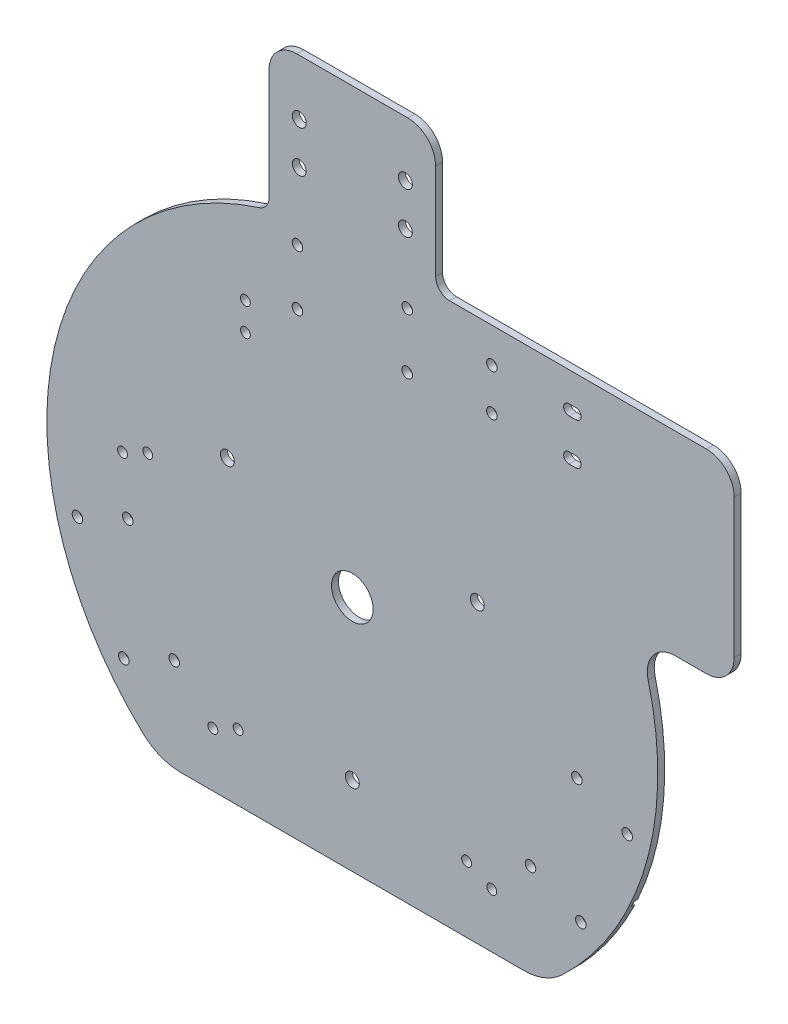
SolidWorks part; units mm, degrees
ref_plane "Front Plane" through (0, 0, 0) normal (0, 0, 1) x (1, 0, 0)
ref_plane "Top Plane" through (0, 0, 0) normal (0, 1, 0) x (1, 0, 0)
ref_plane "Right Plane" through (0, 0, 0) normal (1, 0, 0) x (0, 0, -1)
sketch "Sketch1" plane through (0, 0, 0) normal (0, 0, 1) x (1, 0, 0)
  line L0 (0, 139.7) -> (139.7, 139.7)
  line L2 (139.7, 139.7) -> (174.625, 139.7)
  line L3 (174.625, 139.7) -> (174.625, 50.7007)
  line L4 (174.625, 50.7007) -> (130.175, 50.7007)
  arc A0 (0, 139.7) -> (130.175, 50.7007) centre (0, 0) ccw
  dimension "D1" = 279.4
  dimension "D2" = 139.7
  dimension "D3" = 34.925
  dimension "D4" = 44.45
extrude "Boss-Extrude1" add sketch "Sketch1" along normal blind 3.175
sketch "Sketch2" plane through (0, 0, 0) normal (0, 0, -1) x (-1, 0, 0)
  line L0 (0, -139.7) -> (0, 139.7) construction
  line L1 (-139.7, 0) -> (139.7, 0) construction
  line L2 (-126.6112, -59.0398) -> (-126.6112, 0) construction
  line L3 (126.6112, -59.0398) -> (126.6112, 0) construction
  line L4 (-57.15, 26.6495) -> (0, -72.3372) construction
  line L5 (-126.6112, -59.0398) -> (126.6112, 59.0398) construction
  line L6 (126.6112, -59.0398) -> (-126.6112, 59.0398) construction
  line L7 (-125.9403, -60.4785) -> (127.2821, 57.601)
  line L8 (127.2821, -57.601) -> (-125.9403, 60.4785)
  line L9 (1.5875, -139.7) -> (1.5875, 139.7)
  line L10 (-127.2821, -57.601) -> (125.9403, 60.4785)
  line L11 (125.9403, -60.4785) -> (-127.2821, 57.601)
  line L12 (-1.5875, -139.7) -> (-1.5875, 139.7)
  line L13 (0, -72.3372) -> (57.15, 26.6495) construction
  line L14 (57.15, 26.6495) -> (-57.15, 26.6495) construction
  line L15 (0, 139.7) -> (-174.625, 139.7)
  line L16 (0, 139.7) -> (-174.625, 139.7)
  line L17 (-174.625, 139.7) -> (-174.625, 50.7007)
  line L19 (-121.527, -54.9174) -> (-120.1852, -57.7949)
  line L20 (-120.1852, 57.7949) -> (-121.527, 54.9174)
  line L21 (120.1852, 57.7949) -> (121.527, 54.9174)
  line L22 (-174.625, 139.7) -> (-174.625, 50.7007)
  line L23 (-174.625, 50.7007) -> (-130.175, 50.7007)
  line L24 (-174.625, 50.7007) -> (-130.175, 50.7007)
  line L25 (121.527, -54.9174) -> (120.1852, -57.7949)
  line L26 (-1.5875, 133.35) -> (1.5875, 133.35)
  circle A0 centre (0, 0) radius 139.7 construction
  arc A2 (-130.175, 50.7007) -> (0, 139.7) centre (0, 0) ccw
  arc A3 (-130.175, 50.7007) -> (0, 139.7) centre (0, 0) ccw
  circle A4 centre (-57.15, 26.6495) radius 3.175
  circle A5 centre (57.15, 26.6495) radius 3.175
  circle A6 centre (0, -72.3372) radius 3.175
  point P6 (0, 0)
  point P11 (0, 0)
  arc M9 (-130.175, 50.7007) -> (0, 139.7) centre (0, 0) ccw
  line M24 (0, 139.7) -> (-174.625, 139.7)
  dimension "D5" = 6.35
  dimension "D1" = 25
  dimension "D6" = 114.3
  dimension "D7" = 6.35
  dimension "D8" = 6.35
  dimension "D9" = 6.35
  dimension "D10" = 6.35
  dimension "D11" = 6.35
  dimension "D2" = 1.5875
  dimension "D3" = 1.5875
  dimension "D4" = 0
extrude "Cut-Extrude3" cut sketch "Sketch2" against normal blind 1.5875 contours L12 L7 L11 | L12 L11 L7 L9 L8 L10 | L11 L9 L7 | L11 L12 L10 | L12 L10 L8 | L10 L8 L9 | L9 L7 L8 | L19 L10 L7 M9 | L10 L21 L7 M9 | L8 L25 L11 M9 | L12 L26 L9 M9 M24 region at (123.7323, -57.6973, 0) region at (1.0583, -1.7516, 0) region at (0, 0, 0) region at (-1.0583, -1.7516, 0) region at (2.3104, 0, 0) region at (-123.7323, -57.6973, 0) region at (-2.3104, 0, 0) region at (1.0583, 1.7516, 0) region at (-1.0583, 1.7516, 0) region at (0.0003, 136.5242, 0) region at (-123.7323, 57.6973, 0)
sketch "Sketch3" plane through (0, 0, 3.175) normal (0, 0, 1) x (1, 0, 0)
  circle A0 centre (0, 0) radius 9.525
  dimension "D1" = 19.05
extrude "Cut-Extrude4" cut sketch "Sketch3" against normal through all
extrude "Cut-Extrude5" cut sketch "Sketch2<4>" against normal through all contours L8 A4 L11 | L11 A4 | L8 A4 | L7 A5 L10 | L10 A5 | L7 A5 | L12 A6 | L9 A6 L12 | L9 A6 region at (2.2384, -72.3372, 0) region at (0, -72.3372, 0) region at (-2.2384, -72.3372, 0) region at (58.096, 24.6208, 0) region at (57.15, 26.6495, 0) region at (-57.15, 26.6495, 0) region at (-58.096, 24.6208, 0) region at (56.204, 28.6782, 0) region at (-56.204, 28.6782, 0)
sketch "Sketch2<4>" plane through (0, 0, 0) normal (0, 0, -1) x (-1, 0, 0) same geometry as "Sketch2"
sketch "Sketch4" plane through (0, 0, 3.175) normal (0, 0, 1) x (1, 0, 0)
  line L0 (86.721, 139.7) -> (86.721, 88.9)
  line L1 (86.721, 88.9) -> (139.7, 88.9)
  line L2 (130.175, 50.7007) -> (174.625, 50.7007)
  line L3 (174.625, 139.7) -> (0, 139.7)
  line L5 (174.625, 139.7) -> (0, 139.7)
  line L9 (130.175, 50.7007) -> (174.625, 50.7007)
  line L10 (174.625, 50.7007) -> (174.625, 139.7)
  line L11 (174.625, 50.7007) -> (174.625, 139.7)
  arc A3 (0, 139.7) -> (130.175, 50.7007) centre (0, 0) ccw
  arc A5 (0, 139.7) -> (130.175, 50.7007) centre (0, 0) ccw
  dimension "D3" = 50.8
  dimension "D1" = 0
sketch "Sketch8" plane through (0, 0, 3.175) normal (0, 0, 1) x (1, 0, 0)
  circle A0 centre (25.0825, 101.6) radius 2.413 construction
  circle A1 centre (-25.0825, 101.6) radius 2.413 construction
  circle A2 centre (-25.0825, 127) radius 2.413 construction
  circle A3 centre (25.0825, 127) radius 2.413 construction
  circle A4 centre (102.6812, -20.2056) radius 2.413 construction
  circle A5 centre (125.7014, -30.9401) radius 2.413 construction
  circle A6 centre (81.4805, -65.6705) radius 2.413 construction
  circle A7 centre (104.5008, -76.405) radius 2.413 construction
  circle A8 centre (-81.4805, -65.6705) radius 2.413 construction
  circle A9 centre (-104.5008, -76.405) radius 2.413 construction
  circle A10 centre (-102.6812, -20.2056) radius 2.413 construction
  circle A11 centre (-125.7014, -30.9401) radius 2.413 construction
  circle A12 centre (25.0825, 101.6) radius 2.413
  circle A13 centre (-25.0825, 101.6) radius 2.413
  circle A14 centre (-25.0825, 127) radius 2.413
  circle A15 centre (25.0825, 127) radius 2.413
  circle A16 centre (102.6812, -20.2056) radius 2.413
  circle A17 centre (125.7014, -30.9401) radius 2.413
  circle A18 centre (81.4805, -65.6705) radius 2.413
  circle A19 centre (104.5008, -76.405) radius 2.413
  circle A20 centre (-81.4805, -65.6705) radius 2.413
  circle A21 centre (-104.5008, -76.405) radius 2.413
  circle A22 centre (-102.6812, -20.2056) radius 2.413
  circle A23 centre (-125.7014, -30.9401) radius 2.413
extrude "Cut-Extrude7" cut sketch "Sketch8" against normal through all
sketch "Sketch9" plane through (0, 0, 3.175) normal (0, 0, 1) x (1, 0, 0)
  line L0 (102.235, 123.825) -> (99.06, 123.825) construction
  line L1 (102.235, 121.412) -> (99.06, 121.412)
  line L2 (102.235, 126.238) -> (99.06, 126.238)
  line L3 (100.6475, 123.825) -> (100.6475, 104.775) construction
  line L4 (100.6475, 114.3) -> (63.8175, 114.3) construction
  line L6 (102.235, 104.775) -> (99.06, 104.775) construction
  line L7 (102.235, 107.188) -> (99.06, 107.188)
  line L8 (102.235, 102.362) -> (99.06, 102.362)
  circle A2 centre (100.6475, 104.775) radius 2.413 construction
  circle A3 centre (100.6475, 123.825) radius 2.413 construction
  circle A4 centre (63.8175, 104.775) radius 2.413 construction
  circle A5 centre (63.8175, 123.825) radius 2.413 construction
  circle A8 centre (100.6475, 104.775) radius 2.413
  circle A9 centre (100.6475, 123.825) radius 2.413
  circle A10 centre (63.8175, 104.775) radius 2.413
  circle A11 centre (63.8175, 123.825) radius 2.413
  arc A12 (102.235, 121.412) -> (102.235, 126.238) centre (102.235, 123.825) ccw
  arc A13 (99.06, 126.238) -> (99.06, 121.412) centre (99.06, 123.825) ccw
  arc A14 (102.235, 107.188) -> (102.235, 102.362) centre (102.235, 104.775) cw
  arc A15 (99.06, 102.362) -> (99.06, 107.188) centre (99.06, 104.775) cw
  point P20 (100.6475, 123.825)
  point P29 (100.6475, 104.775)
  dimension "D1" = 4.826
  dimension "D2" = 3.175
extrude "Cut-Extrude8" cut sketch "Sketch9" against normal through all contours A9 | A11 | A10 | A8 | L2 A13 L1 A9 | L1 A12 L2 A9 | A15 L8 A8 L7 | A14 L7 A8 L8 region at (103.3364, 123.825, 3.175) region at (97.9586, 123.825, 3.175) region at (100.6475, 123.825, 3.175) region at (103.3364, 104.775, 3.175) region at (97.9586, 104.775, 3.175) region at (100.6475, 104.775, 3.175) region at (63.8175, 104.775, 3.175) region at (63.8175, 123.825, 3.175)
fillet "Fillet1" radius 12.7 3 edges at (174.625, 50.7007, 1.5875) (174.625, 139.7, 1.5875) (130.175, 50.7007, 1.5875)
sketch "Sketch10" plane through (0, 0, 3.175) normal (0, 0, 1) x (1, 0, 0)
  line L0 (-87.8942, -108.585) -> (87.8942, -108.585)
  line L3 (147.5863, 50.7007) -> (161.925, 50.7007)
  line L4 (174.625, 63.4007) -> (174.625, 127)
  line L5 (161.925, 139.7) -> (0, 139.7)
  line L6 (147.5863, 50.7007) -> (161.925, 50.7007)
  line L7 (174.625, 63.4007) -> (174.625, 127)
  line L8 (161.925, 139.7) -> (0, 139.7)
  arc A4 (161.925, 50.7007) -> (174.625, 63.4007) centre (161.925, 63.4007) ccw
  arc A5 (174.625, 127) -> (161.925, 139.7) centre (161.925, 127) ccw
  arc A6 (0, 139.7) -> (135.2874, 34.834) centre (0, 0) ccw
  arc A7 (147.5863, 50.7007) -> (135.2874, 34.834) centre (147.5863, 38.0007) ccw
  arc A8 (161.925, 50.7007) -> (174.625, 63.4007) centre (161.925, 63.4007) ccw
  arc A9 (174.625, 127) -> (161.925, 139.7) centre (161.925, 127) ccw
  arc A10 (0, 139.7) -> (135.2874, 34.834) centre (0, 0) ccw
  arc A11 (147.5863, 50.7007) -> (135.2874, 34.834) centre (147.5863, 38.0007) ccw
  arc M36 (0, 139.7) -> (135.2874, 34.834) centre (0, 0) ccw
  dimension "D2" = 108.585
  dimension "D1" = 0
extrude "Cut-Extrude9" cut sketch "Sketch10" against normal through all contours L0 M36 region at (0, -121.158, 3.175)
fillet "Fillet2" radius 25.4 2 edges at (87.8942, -108.585, 1.5875) (-87.8942, -108.585, 1.5875)
sketch "Sketch11" plane through (0, 0, 3.175) normal (0, 0, 1) x (1, 0, 0)
  circle A0 centre (52.2526, -78.3155) radius 2.032 construction
  circle A1 centre (63.7627, -83.6827) radius 2.032 construction
  circle A2 centre (-48.895, 80.4545) radius 2.032 construction
  circle A3 centre (-48.895, 93.1545) radius 2.032 construction
  circle A4 centre (-63.7627, -83.6827) radius 2.032 construction
  circle A5 centre (-52.2526, -78.3155) radius 2.032 construction
  circle A6 centre (-105.0906, 4.9451) radius 2.032 construction
  circle A7 centre (-93.5805, 10.3124) radius 2.032 construction
  circle A8 centre (52.2526, -78.3155) radius 2.032 construction
  circle A9 centre (63.7627, -83.6827) radius 2.032 construction
  circle A10 centre (-48.895, 80.4545) radius 2.032 construction
  circle A11 centre (-48.895, 93.1545) radius 2.032 construction
  circle A12 centre (-63.7627, -83.6827) radius 2.032 construction
  circle A13 centre (-52.2526, -78.3155) radius 2.032 construction
  circle A14 centre (-105.0906, 4.9451) radius 2.032 construction
  circle A15 centre (-93.5805, 10.3124) radius 2.032 construction
  circle A16 centre (-93.5805, 10.3124) radius 2.2479
  circle A17 centre (-105.0906, 4.9451) radius 2.2479
  circle A18 centre (-52.2526, -78.3155) radius 2.2479
  circle A19 centre (-63.7627, -83.6827) radius 2.2479
  circle A20 centre (52.2526, -78.3155) radius 2.2479
  circle A21 centre (63.7627, -83.6827) radius 2.2479
  circle A22 centre (-48.895, 93.1545) radius 2.2479
  circle A23 centre (-48.895, 80.4545) radius 2.2479
  dimension "D1" = 4.4958
extrude "Cut-Extrude10" cut sketch "Sketch11" against normal through all
sketch "Sketch12" plane through (0, 0, 0) normal (0, 0, -1) x (-1, 0, 0)
  line L0 (0, 0) -> (0, 50000) construction
  line L1 (-24.257, 9.525) -> (24.257, 9.525) construction
  line L2 (-24.257, 9.525) -> (-24.257, -9.525) construction
  line L3 (-24.257, -9.525) -> (24.257, -9.525) construction
  line L4 (24.257, 9.525) -> (24.257, -9.525) construction
  line L5 (-24.257, 9.525) -> (24.257, -9.525) construction
  line L6 (-24.257, -9.525) -> (24.257, 9.525) construction
  line L22 (-78.3884, -108.585) -> (78.3884, -108.585)
  line L23 (125.9321, -60.4747) -> (120.1852, -57.7949)
  line L24 (120.1852, -57.7949) -> (121.527, -54.9174)
  line L25 (121.527, -54.9174) -> (127.2739, -57.5972)
  line L26 (127.2739, 57.5972) -> (121.527, 54.9174)
  line L27 (121.527, 54.9174) -> (120.1852, 57.7949)
  line L28 (120.1852, 57.7949) -> (125.9321, 60.4747)
  line L29 (1.5875, 139.691) -> (1.5875, 133.35)
  line L30 (1.5875, 133.35) -> (-1.5875, 133.35)
  line L31 (-1.5875, 133.35) -> (-1.5875, 139.7)
  line L32 (-1.5875, 139.7) -> (-161.925, 139.7)
  line L33 (-174.625, 127) -> (-174.625, 63.4007)
  line L34 (-161.925, 50.7007) -> (-147.5863, 50.7007)
  line L35 (-127.2739, -57.5972) -> (-121.527, -54.9174)
  line L36 (-121.527, -54.9174) -> (-120.1852, -57.7949)
  line L37 (-120.1852, -57.7949) -> (-125.9321, -60.4747)
  line L38 (-78.3884, -108.585) -> (78.3884, -108.585)
  line L39 (125.9321, -60.4747) -> (120.1852, -57.7949)
  line L40 (120.1852, -57.7949) -> (121.527, -54.9174)
  line L41 (121.527, -54.9174) -> (127.2739, -57.5972)
  line L42 (127.2739, 57.5972) -> (121.527, 54.9174)
  line L43 (121.527, 54.9174) -> (120.1852, 57.7949)
  line L44 (120.1852, 57.7949) -> (125.9321, 60.4747)
  line L45 (1.5875, 139.691) -> (1.5875, 133.35)
  line L46 (1.5875, 133.35) -> (-1.5875, 133.35)
  line L47 (-1.5875, 133.35) -> (-1.5875, 139.7)
  line L48 (-1.5875, 139.7) -> (-161.925, 139.7)
  line L49 (-174.625, 127) -> (-174.625, 63.4007)
  line L50 (-161.925, 50.7007) -> (-147.5863, 50.7007)
  line L51 (-127.2739, -57.5972) -> (-121.527, -54.9174)
  line L52 (-121.527, -54.9174) -> (-120.1852, -57.7949)
  line L53 (-120.1852, -57.7949) -> (-125.9321, -60.4747)
  circle A0 centre (-24.257, 9.525) radius 3.175
  circle A1 centre (24.257, 9.525) radius 3.175
  circle A2 centre (24.257, -9.525) radius 3.175
  circle A3 centre (-24.257, -9.525) radius 3.175
  arc A14 (-125.9321, -60.4747) -> (-95.8081, -101.6706) centre (0, 0) ccw
  arc A15 (-95.8081, -101.6706) -> (-78.3884, -108.585) centre (-78.3884, -83.185) ccw
  arc A16 (78.3884, -108.585) -> (95.8081, -101.6706) centre (78.3884, -83.185) ccw
  arc A17 (95.8081, -101.6706) -> (125.9321, -60.4747) centre (0, 0) ccw
  arc A18 (127.2739, -57.5972) -> (127.2739, 57.5972) centre (0, 0) ccw
  arc A19 (125.9321, 60.4747) -> (1.5875, 139.691) centre (0, 0) ccw
  arc A20 (-161.925, 139.7) -> (-174.625, 127) centre (-161.925, 127) ccw
  arc A21 (-174.625, 63.4007) -> (-161.925, 50.7007) centre (-161.925, 63.4007) ccw
  arc A22 (-135.2874, 34.834) -> (-147.5863, 50.7007) centre (-147.5863, 38.0007) ccw
  arc A23 (-135.2874, 34.834) -> (-127.2739, -57.5972) centre (0, 0) ccw
  arc A24 (-125.9321, -60.4747) -> (-95.8081, -101.6706) centre (0, 0) ccw
  arc A25 (-95.8081, -101.6706) -> (-78.3884, -108.585) centre (-78.3884, -83.185) ccw
  arc A26 (78.3884, -108.585) -> (95.8081, -101.6706) centre (78.3884, -83.185) ccw
  arc A27 (95.8081, -101.6706) -> (125.9321, -60.4747) centre (0, 0) ccw
  arc A28 (127.2739, -57.5972) -> (127.2739, 57.5972) centre (0, 0) ccw
  arc A29 (125.9321, 60.4747) -> (1.5875, 139.691) centre (0, 0) ccw
  arc A30 (-161.925, 139.7) -> (-174.625, 127) centre (-161.925, 127) ccw
  arc A31 (-174.625, 63.4007) -> (-161.925, 50.7007) centre (-161.925, 63.4007) ccw
  arc A32 (-135.2874, 34.834) -> (-147.5863, 50.7007) centre (-147.5863, 38.0007) ccw
  arc A33 (-135.2874, 34.834) -> (-127.2739, -57.5972) centre (0, 0) ccw
  point P0 (0, 0)
  dimension "D3" = 6.35
  dimension "D1" = 48.514
  dimension "D2" = 19.05
  dimension "D4" = 0
sketch "Sketch14" plane through (0, 0, 0) normal (0, 0, -1) x (-1, 0, 0)
  line L0 (0, 0) -> (0, 50000) construction
  line L1 (-38.1, 139.7) -> (-38.1, 202.565)
  line L2 (-161.925, 139.7) -> (-1.5875, 139.7) construction
  line L3 (-38.1, 202.565) -> (38.1, 202.565)
  line L4 (38.1, 202.565) -> (38.1, 134.4042)
  line L6 (-24.257, 177.165) -> (24.257, 177.165) construction
  line L7 (-24.257, 177.165) -> (-24.257, 158.115) construction
  line L8 (-24.257, 158.115) -> (24.257, 158.115) construction
  line L9 (24.257, 177.165) -> (24.257, 158.115) construction
  line L10 (-24.257, 177.165) -> (24.257, 158.115) construction
  line L11 (-24.257, 158.115) -> (24.257, 177.165) construction
  line L12 (-38.1, 139.7) -> (0, 139.7)
  arc A0 (125.9321, 60.4747) -> (1.5875, 139.691) centre (0, 0) ccw construction
  circle A1 centre (-24.257, 177.165) radius 3.175
  circle A2 centre (24.257, 177.165) radius 3.175
  circle A3 centre (24.257, 158.115) radius 3.175
  circle A4 centre (-24.257, 158.115) radius 3.175
  arc A5 (38.1, 134.4042) -> (0, 139.7) centre (0, 0) ccw
  point P7 (0, 202.565)
  point P13 (0, 167.64)
  dimension "D6" = 6.35
  dimension "D1" = 76.2
  dimension "D2" = 48.514
  dimension "D3" = 19.05
  dimension "D4" = 167.64
  dimension "D5" = 25.4
extrude "Boss-Extrude2" add sketch "Sketch14" against normal up to surface (3.175 mm away) up to face at (54.5005, -78.3155, 3.175)
fillet "Fillet3" radius 12.7 2 edges at (-38.1, 202.565, 1.5875) (38.1, 202.565, 1.5875)
fillet "Fillet4" radius 6.35 2 edges at (-38.1, 134.4042, 1.5875) (38.1, 139.7, 1.5875)
